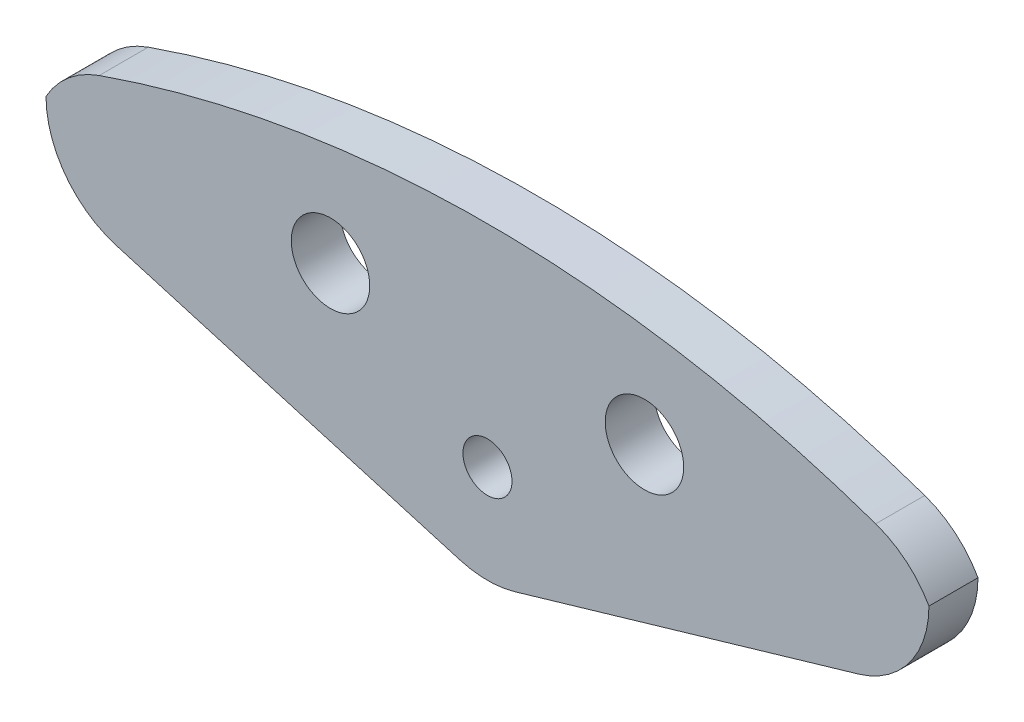
SolidWorks part; units mm, degrees
ref_plane "Front Plane" through (0, 0, 0) normal (0, 0, 1) x (1, 0, 0)
ref_plane "Top Plane" through (0, 0, 0) normal (0, 1, 0) x (1, 0, 0)
ref_plane "Right Plane" through (0, 0, 0) normal (1, 0, 0) x (0, 0, -1)
sketch "Sketch1" plane through (0, 0, 0) normal (0, 0, 1) x (1, 0, 0)
  line L0 (-57.4671, 21.5) -> (58.0784, 21.5) construction
  line L1 (0, 0) -> (0, 18.7938) construction
  line L16 (45, 12.743) -> (45, 2.743)
  line L17 (45, 2.743) -> (2.8073, -9.5979)
  line L19 (-45, 12.743) -> (-45, 2.743)
  line L20 (-45, 2.743) -> (-2.8073, -9.5979)
  circle A2 centre (16, 10) radius 11.5 construction
  circle A8 centre (0, 0) radius 2.5
  arc A10 (-2.8073, -9.5979) -> (2.8073, -9.5979) centre (0, 0) ccw
  arc A11 (-45, 12.743) -> (45, 12.743) centre (0, -98.5) cw
  circle A12 centre (16, 10) radius 4
  circle A13 centre (-16, 10) radius 4
  point P14 (0, 0)
  point P16 (0, 0)
  point P18 (44.0752, 13.1126)
  point P19 (0, 0)
  point P20 (0, 0)
  point P21 (0, -12)
  point P22 (0, 0)
  dimension "D1" = 21.5
  dimension "D3" = 10
  dimension "D4" = 8
  dimension "D7" = 90
  dimension "D5" = 5
  dimension "D6" = 10
  dimension "D2" = 120
extrude "Boss-Extrude1" add sketch "Sketch1" along normal blind 5
fillet "Fillet1" radius 10 2 edges at (-45, 2.743, 2.5) (45, 2.743, 2.5)
fillet "Fillet2" radius 10 2 edges at (45, 12.743, 2.5) (-45, 12.743, 2.5)
